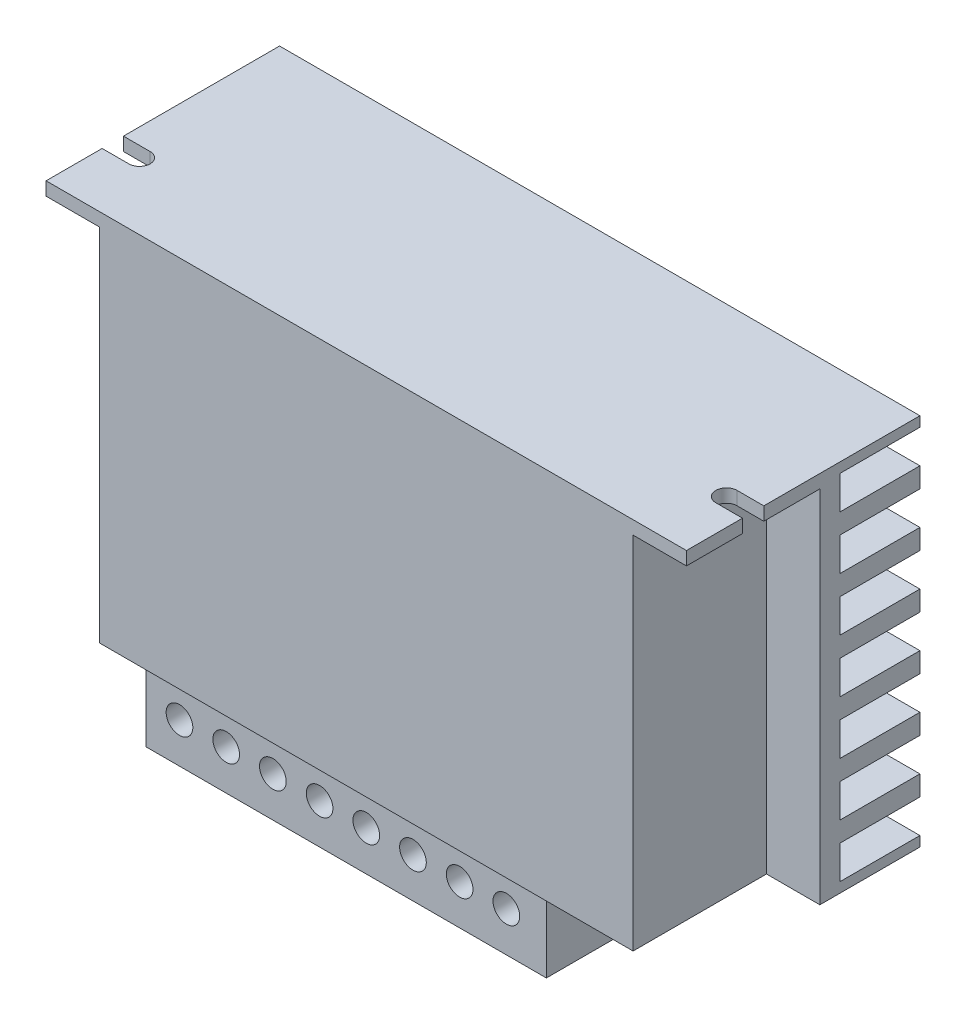
SolidWorks part; units mm, degrees
material "Простая углеродистая сталь"
ref_plane "Спереди" through (0, 0, 0) normal (0, 0, 1) x (1, 0, 0)
ref_plane "Сверху" through (0, 0, 0) normal (0, 1, 0) x (1, 0, 0)
ref_plane "Справа" through (0, 0, 0) normal (1, 0, 0) x (0, 0, -1)
sketch "Эскиз1" plane through (0, 0, 0) normal (0, 0, 1) x (1, 0, 0)
  line L0 (0, 0) -> (96, 0)
  line L1 (0, 0) -> (0, 56)
  line L2 (96, 0) -> (96, 56)
  line L3 (0, 56) -> (96, 56)
  dimension "D1" = 56
  dimension "D2" = 96
extrude "Бобышка-Вытянуть1" add sketch "Эскиз1" along normal blind 35
sketch "Эскиз5" plane through (96, 0, 0) normal (1, 0, 0) x (0, 0, -1)
  line L0 (-35, 54) -> (-15, 54)
  line L1 (-15, 54) -> (-15, 0)
  line L2 (-35, 56) -> (0, 56) construction
  line L3 (0, 0) -> (0, 56) construction
  line L4 (0, 0) -> (0, 56)
  line L5 (0, 56) -> (-35, 56)
  line L6 (-35, 56) -> (-35, 0)
  line L7 (-35, 0) -> (0, 0)
  line L10 (-35, 54) -> (-35, 0)
  line L11 (-35, 0) -> (-15, 0)
  dimension "D2" = 2
  dimension "D3" = 15
  dimension "D1" = 0
extrude "Вырез-Вытянуть3" cut sketch "Эскиз5" against normal blind 8
sketch "Эскиз6" plane through (0, 0, 0) normal (-1, 0, 0) x (0, 0, 1)
  line L4 (35, 0) -> (35, 54)
  line L5 (15, 0) -> (35, 0)
  line L6 (15, 54) -> (15, 0)
  line L7 (35, 54) -> (15, 54)
  line L8 (35, 0) -> (35, 54)
  line L9 (15, 0) -> (35, 0)
  line L10 (15, 54) -> (15, 0)
  line L11 (35, 54) -> (15, 54)
  dimension "D1" = 0
extrude "Вырез-Вытянуть4" cut sketch "Эскиз6" against normal blind 8
sketch "Эскиз7" plane through (96, 0, 0) normal (1, 0, 0) x (0, 0, -1)
  line L0 (-12, 1.5) -> (-12, 6.5)
  line L1 (-12, 1.5) -> (0, 1.5)
  line L2 (-12, 6.5) -> (0, 6.5)
  line L3 (0, 1.5) -> (0, 6.5)
  line L4 (0, 0) -> (0, 56) construction
  line L5 (-15, 0) -> (0, 0) construction
  line L6 (0, 9.5) -> (0, 14.5)
  line L7 (-12, 14.5) -> (0, 14.5)
  line L8 (-12, 9.5) -> (-12, 14.5)
  line L9 (-12, 9.5) -> (0, 9.5)
  line L10 (0, 17.5) -> (0, 22.5)
  line L11 (-12, 22.5) -> (0, 22.5)
  line L12 (-12, 17.5) -> (-12, 22.5)
  line L13 (-12, 17.5) -> (0, 17.5)
  line L14 (0, 25.5) -> (0, 30.5)
  line L15 (-12, 30.5) -> (0, 30.5)
  line L16 (-12, 25.5) -> (-12, 30.5)
  line L17 (-12, 25.5) -> (0, 25.5)
  line L18 (0, 33.5) -> (0, 38.5)
  line L19 (-12, 38.5) -> (0, 38.5)
  line L20 (-12, 33.5) -> (-12, 38.5)
  line L21 (-12, 33.5) -> (0, 33.5)
  line L22 (0, 41.5) -> (0, 46.5)
  line L23 (-12, 46.5) -> (0, 46.5)
  line L24 (-12, 41.5) -> (-12, 46.5)
  line L25 (-12, 41.5) -> (0, 41.5)
  line L26 (0, 49.5) -> (0, 54.5)
  line L27 (-12, 54.5) -> (0, 54.5)
  line L28 (-12, 49.5) -> (-12, 54.5)
  line L29 (-12, 49.5) -> (0, 49.5)
  line L30 (-35, 56) -> (0, 56) construction
  point P4 (-7.5, 0)
  dimension "D1" = 1.5
  dimension "D2" = 5
  dimension "D3" = 12
  dimension "D5" = 8
  dimension "D6" = 1.5
  dimension "D4" = 7
extrude "Вырез-Вытянуть5" cut sketch "Эскиз7" against normal through all
sketch "Эскиз8" plane through (0, 54, 0) normal (0, -1, 0) x (1, 0, 0)
  line L0 (88, 25) -> (96, 25) construction
  line L1 (88, 15) -> (88, 35) construction
  line L2 (96, 15) -> (96, 35) construction
  line L3 (92, 26.6) -> (96, 26.6)
  line L4 (96, 26.6) -> (96, 23.4)
  line L5 (96, 23.4) -> (92, 23.4)
  line L6 (96, 35) -> (0, 35) construction
  line L7 (48, 35) -> (48, 19.7888) construction
  line L8 (96, 26.6) -> (92, 26.6)
  line L9 (92, 23.4) -> (96, 23.4)
  line L10 (8, 25) -> (0, 25) construction
  line L11 (4, 23.4) -> (0, 23.4)
  line L12 (0, 26.6) -> (4, 26.6)
  line L13 (0, 23.4) -> (4, 23.4)
  line L14 (0, 26.6) -> (0, 23.4)
  line L15 (4, 26.6) -> (0, 26.6)
  arc A0 (92, 26.6) -> (92, 23.4) centre (92, 25) ccw
  arc A1 (4, 26.6) -> (4, 23.4) centre (4, 25) cw
  line M1 (96, 15) -> (96, 35)
  dimension "D1" = 3.2
extrude "Вырез-Вытянуть7" cut sketch "Эскиз8" against normal through all contours A1 L12 L14 L11 | L3 A0 L5 M1 region at (93.3596, 54, 25) region at (2.6404, 54, 25)
sketch "Эскиз9" plane through (0, 0, 0) normal (0, -1, 0) x (1, 0, 0)
  line L0 (13, 33) -> (73, 33)
  line L1 (13, 33) -> (13, 18)
  line L2 (73, 33) -> (73, 18)
  line L3 (13, 18) -> (73, 18)
  line L4 (8, 35) -> (88, 35) construction
  line L5 (8, 15) -> (8, 35) construction
  dimension "D1" = 2
  dimension "D2" = 5
  dimension "D3" = 60
  dimension "D4" = 15
extrude "Бобышка-Вытянуть2" add sketch "Эскиз9" along normal blind 12
sketch "Эскиз10" plane through (0, 0, 33) normal (0, 0, 1) x (1, 0, 0)
  line L0 (13, -6) -> (73, -6) construction
  line L1 (13, -12) -> (13, 0) construction
  line L2 (73, -12) -> (73, 0) construction
  line L3 (20, -6) -> (80, -6) construction
  line L4 (27, -6) -> (87, -6) construction
  line L5 (34, -6) -> (94, -6) construction
  line L6 (41, -6) -> (101, -6) construction
  line L7 (48, -6) -> (108, -6) construction
  line L8 (55, -6) -> (115, -6) construction
  line L9 (62, -6) -> (122, -6) construction
  circle A0 centre (18, -6) radius 2
  circle A1 centre (25, -6) radius 2
  circle A2 centre (32, -6) radius 2
  circle A3 centre (39, -6) radius 2
  circle A4 centre (46, -6) radius 2
  circle A5 centre (53, -6) radius 2
  circle A6 centre (60, -6) radius 2
  circle A7 centre (67, -6) radius 2
  dimension "D1" = 4
  dimension "D2" = 5
  dimension "D4" = 7
  dimension "D3" = 8
extrude "Вырез-Вытянуть8" cut sketch "Эскиз10" against normal blind 3
sketch "Эскиз11" plane through (0, 0, 0) normal (0, 0, -1) x (-1, 0, 0)
  line L0 (-23, 63) -> (-73, 63) construction
  line L1 (-23, 63) -> (-23, 13) construction
  line L2 (-73, 63) -> (-73, 13) construction
  line L3 (-23, 13) -> (-73, 13) construction
  circle A0 centre (-23, 63) radius 2.1 construction
  circle A1 centre (-23, 63) radius 2.1 construction
  circle A2 centre (-73, 63) radius 2.1 construction
  circle A3 centre (-73, 63) radius 2.1 construction
  circle A4 centre (-23, 13) radius 2.1
  circle A5 centre (-73, 13) radius 2.1
  dimension "D1" = 50
extrude "Вырез-Вытянуть9" cut sketch "Эскиз11" against normal blind 15
